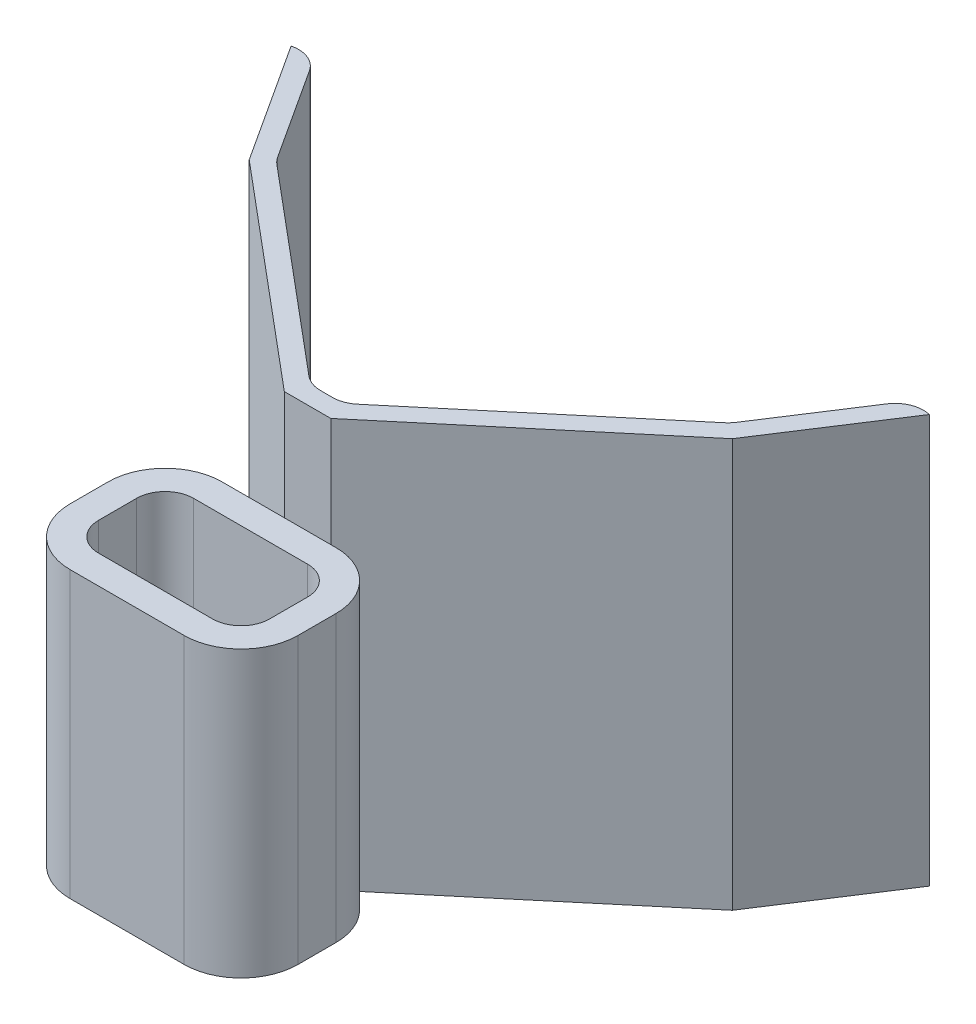
SolidWorks part; units mm, degrees
ref_plane "Alzado" through (0, 0, 0) normal (0, 0, 1) x (1, 0, 0)
ref_plane "Planta" through (0, 0, 0) normal (0, 1, 0) x (1, 0, 0)
ref_plane "Vista lateral" through (0, 0, 0) normal (1, 0, 0) x (0, 0, -1)
sketch "Croquis1" plane through (0, 0, 0) normal (0, 1, 0) x (1, 0, 0)
  line L0 (-6, 8) -> (6, 8)
  line L1 (-6, -5) -> (6, -5)
  line L2 (-9, -2) -> (-9, 2)
  line L3 (-6, 5) -> (6, 5)
  line L4 (9, -2) -> (9, 2)
  line L5 (-9, -5) -> (9, 5) construction
  line L6 (-9, 5) -> (9, -5) construction
  line L7 (12, -2) -> (12, 2)
  line L8 (-6, -8) -> (6, -8)
  line L9 (-12, -2) -> (-12, 2)
  arc A0 (6, 5) -> (9, 2) centre (6, 2) cw
  arc A1 (6, -5) -> (9, -2) centre (6, -2) ccw
  arc A2 (-6, -5) -> (-9, -2) centre (-6, -2) cw
  arc A3 (-9, 2) -> (-6, 5) centre (-6, 2) cw
  arc A4 (6, 8) -> (12, 2) centre (6, 2) cw
  arc A5 (6, -8) -> (12, -2) centre (6, -2) ccw
  arc A6 (-6, -8) -> (-12, -2) centre (-6, -2) cw
  arc A7 (-12, 2) -> (-6, 8) centre (-6, 2) cw
  point P0 (0, 0)
  dimension "D3" = 3
  dimension "D1" = 10
  dimension "D2" = 18
  dimension "D4" = 3
extrude "Saliente-Extruir1" add sketch "Croquis1" along normal blind 30
sketch "Croquis3" plane through (0, 0, -8) normal (0, 0, -1) x (-1, 0, 0)
  line L0 (0, 15) -> (0, 0) construction
  line L1 (-2.4468, 12.9911) -> (2.4468, 12.9911)
  line L2 (-2.4468, 12.9911) -> (-2.4468, 17.0089)
  line L3 (-2.4468, 17.0089) -> (2.4468, 17.0089)
  line L4 (2.4468, 12.9911) -> (2.4468, 17.0089)
  line L5 (-2.4468, 12.9911) -> (2.4468, 17.0089) construction
  line L6 (-2.4468, 17.0089) -> (2.4468, 12.9911) construction
  point P0 (0, 15)
extrude "Saliente-Extruir2" add sketch "Croquis3" along normal blind 3
sketch "Croquis7" plane through (0, 17.0089, 0) normal (0, 1, 0) x (1, 0, 0)
  line L0 (0, 11) -> (0, 15.2379) construction
  line L1 (-2.4468, 11) -> (2.4468, 11) construction
  line L2 (-2.4468, 11) -> (2.4468, 11)
  line L9 (-2.4468, 11) -> (-25.4281, 30.2836)
  line L10 (2.4468, 11) -> (25.4281, 30.2836)
  line L11 (-25.4281, 30.2836) -> (-33.5977, 42.8637)
  line L12 (25.4281, 30.2836) -> (33.5977, 42.8637)
  line L13 (23.9135, 31.6236) -> (31.9203, 43.953)
  line L14 (1.7188, 13) -> (23.9135, 31.6236)
  line L15 (-1.7188, 13) -> (1.7188, 13)
  line L16 (-1.7188, 13) -> (-23.9135, 31.6236)
  line L17 (-23.9135, 31.6236) -> (-31.9203, 43.953)
  line L18 (-33.5977, 42.8637) -> (-31.9203, 43.953)
  line L19 (31.9203, 43.953) -> (33.5977, 42.8637)
  dimension "D1" = 140
  dimension "D2" = 30
  dimension "D3" = 163
  dimension "D4" = 15
  dimension "D5" = 2
extrude "Saliente-Extruir3" add sketch "Croquis7" along normal mid plane 43
fillet "Redondeo2" radius 3 6 edges at (31.9203, 17.0089, -43.953) (-31.9203, 17.0089, -43.953) (-23.9135, 17.0089, -31.6236) (23.9135, 17.0089, -31.6236) (1.7188, 17.0089, -13) (-1.7188, 17.0089, -13)
